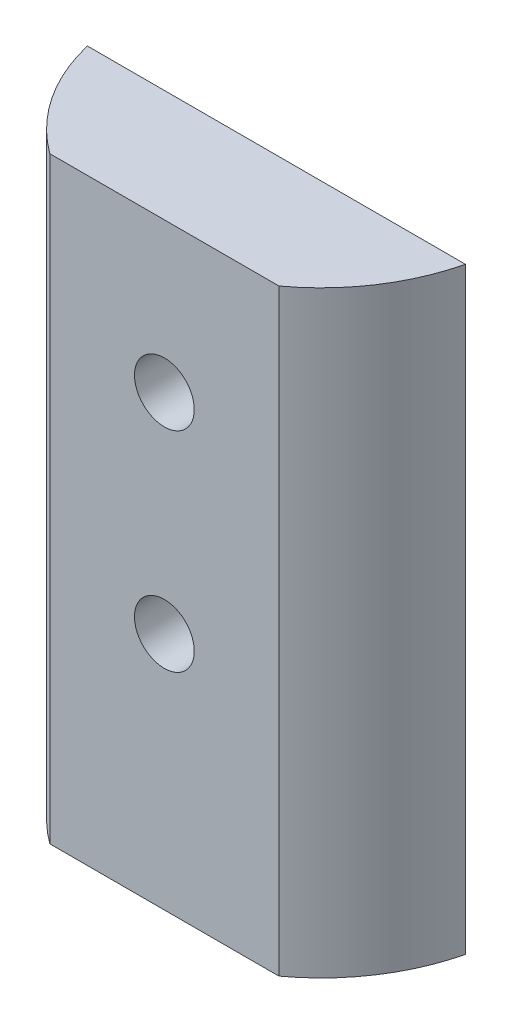
SolidWorks part; units mm, degrees
ref_plane "前视基准面" through (0, 0, 0) normal (0, 0, 1) x (1, 0, 0)
ref_plane "上视基准面" through (0, 0, 0) normal (0, 1, 0) x (1, 0, 0)
ref_plane "右视基准面" through (0, 0, 0) normal (1, 0, 0) x (0, 0, -1)
other "Configuration Table"
sketch "草图2" plane through (0, 0, 0) normal (0, 1, 0) x (1, 0, 0)
  line L0 (-6.3246, -1.5) -> (6.3246, -1.5)
  line L1 (-6.5, 0) -> (6.5, 0)
  line L2 (-3.8324, -5.25) -> (3.8324, -5.25)
  circle A0 centre (0, 0) radius 6.5
  dimension "D1" = 13
  dimension "D2" = 3.75
  dimension "D3" = 1.5
extrude "凸台-拉伸1" add sketch "草图2" along normal blind 20 contours L2 A0 L0 region at (0, 0, 3.2362)
sketch "草图3" plane through (0, 0, 5.25) normal (0, 0, 1) x (1, 0, 0)
  line L0 (-3.8324, 0) -> (3.8324, 0) construction
  circle A0 centre (0, 15) radius 1
  circle A1 centre (0, 8) radius 1
  dimension "D3" = 2
  dimension "D1" = 15
  dimension "D2" = 8
extrude "切除-拉伸1" cut sketch "草图3" against normal blind 20
